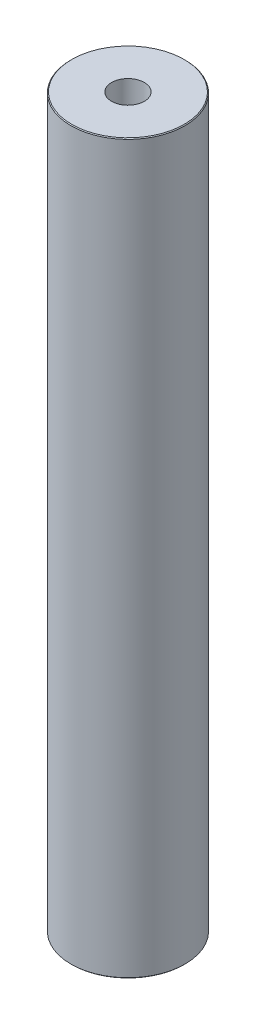
SolidWorks part; units mm, degrees
ref_plane "Front Plane" through (0, 0, 0) normal (0, 0, 1) x (1, 0, 0)
ref_plane "Top Plane" through (0, 0, 0) normal (0, 1, 0) x (1, 0, 0)
ref_plane "Right Plane" through (0, 0, 0) normal (1, 0, 0) x (0, 0, -1)
sketch "Sketch1" plane through (0, 0, 0) normal (0, 1, 0) x (1, 0, 0)
  circle A0 centre (0, 0) radius 42.5
  dimension "SHAFT_OD" = 85
extrude "Boss-Extrude1" add sketch "Sketch1" along normal blind 542.3254
sketch "Sketch2" plane through (0, 0, 0) normal (0, 1, 0) x (1, 0, 0)
  circle A0 centre (0, 0) radius 12.2007
  dimension "BORE_D" = 24.4014
extrude "Cut-Extrude1" cut sketch "Sketch2" along normal through all
chamfer "Chamfer1" distance 0.5919 angle 45 2 edges at (0, 542.3254, 42.5) (0, 0, 42.5)
